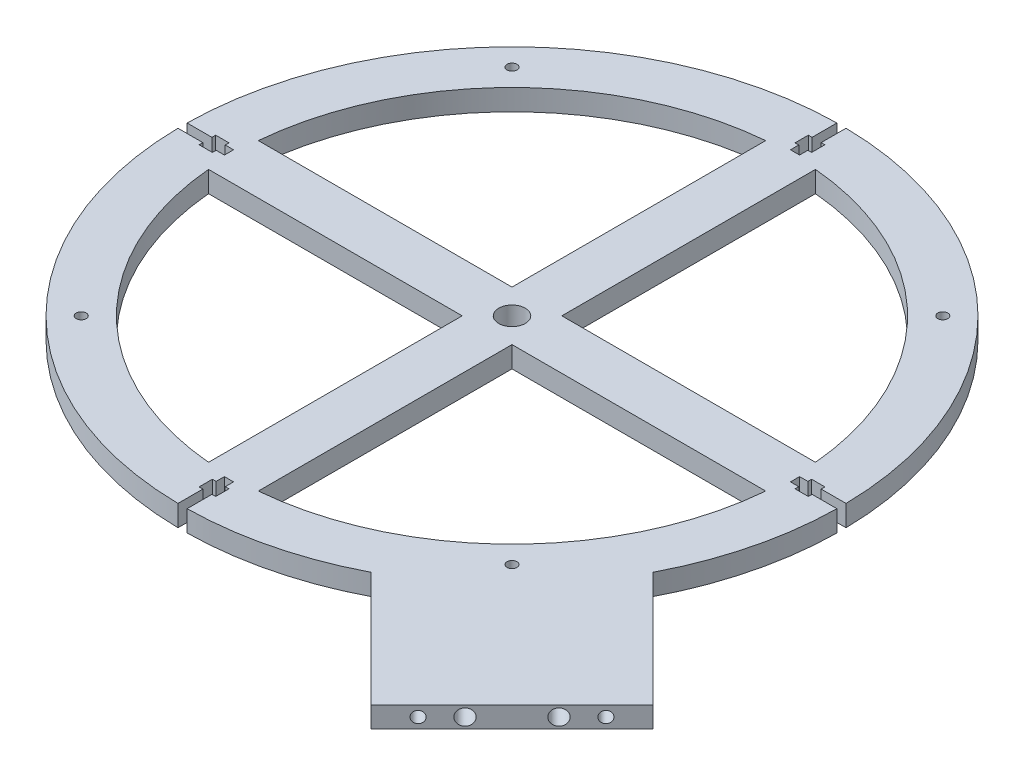
SolidWorks part; units mm, degrees
material "6061 Alloy"
ref_plane "Front Plane" through (0, 0, 0) normal (0, 0, 1) x (1, 0, 0)
ref_plane "Top Plane" through (0, 0, 0) normal (0, 1, 0) x (1, 0, 0)
ref_plane "Right Plane" through (0, 0, 0) normal (1, 0, 0) x (0, 0, -1)
sketch "Sketch1" plane through (0, 0, 0) normal (0, 1, 0) x (1, 0, 0)
  line L0 (0, -99.238) -> (0, 99.238) construction
  line L1 (-99.238, 0) -> (99.238, 0) construction
  line L2 (-98.9542, -7.5) -> (98.9542, -7.5)
  line L3 (7.5, -98.9542) -> (7.5, 98.9542)
  line L4 (-98.9542, 7.5) -> (98.9542, 7.5)
  line L5 (-7.5, -98.9542) -> (-7.5, 98.9542)
  line L6 (-7.5, -99.238) -> (-7.5, 99.238) construction
  line L7 (7.5, -99.238) -> (7.5, 99.238) construction
  line L8 (-99.238, -7.5) -> (99.238, -7.5) construction
  line L9 (-99.238, 7.5) -> (99.238, 7.5) construction
  line L11 (80.2566, -122.683) -> (122.683, -80.2566)
  line L16 (101.4698, -101.4698) -> (70.1719, -70.1719) construction
  line L17 (122.683, -80.2566) -> (88.1018, -45.6754)
  line L23 (80.2566, -122.683) -> (45.6754, -88.1018)
  line L33 (122.683, -80.2566) -> (91.3851, -48.9587) construction
  line L34 (80.2566, -122.683) -> (48.9587, -91.3851) construction
  circle A0 centre (0, 0) radius 100 construction
  circle A1 centre (0, 0) radius 99.238
  circle A2 centre (0, 0) radius 84.238
  point P7 (0, 0)
  point P11 (0, 0)
  dimension "D1" = 200
  dimension "D2" = 0.762
  dimension "D3" = 15
  dimension "D6" = 45
  dimension "D8" = 43.5
  dimension "D4" = 7.5
  dimension "D5" = 7.5
  dimension "D11" = 30
  dimension "D12" = 30
extrude "Boss-Extrude1" add sketch "Sketch1" along normal mid plane 6.35 contours A2 L2 A1 L5 | A2 L4 A1 L2 | A2 L5 A1 L4 | A2 L3 A1 L5 | A2 L4 A1 L3 | A2 L2 A1 L4 | A2 L3 A1 L2 | A2 L5 A1 L3 | L5 A2 L3 L2 | L4 A2 L2 L5 | L3 A2 L5 L4 | L2 A2 L4 L3 | L5 L2 L3 L4 | A1 | A1 L23 L17 region at (-91.6349, 0, 0) region at (-59.7933, 0, 59.7933) region at (-45.8134, 0, 0) region at (-59.7933, 0, -59.7933) region at (0, 0, 91.6349) region at (0, 0, 0) region at (0, 0, 45.8134) region at (0, 0, -91.6349) region at (59.7933, 0, 59.7933) region at (45.8134, 0, 0) region at (0, 0, -45.8134) region at (59.7933, 0, -59.7933) region at (85.2642, 0, 85.2642) region at (91.6349, 0, 0)
sketch "Sketch2" plane through (0, 0, 0) normal (0, 1, 0) x (1, 0, 0)
  line L0 (-1.375, 85.238) -> (-1.375, 99.238)
  line L1 (-1.375, 85.238) -> (1.375, 85.238)
  line L2 (-1.375, 99.238) -> (1.375, 99.238)
  line L3 (1.375, 85.238) -> (1.375, 99.238)
  line L4 (-1.375, 85.238) -> (1.375, 99.238) construction
  line L5 (-1.375, 99.238) -> (1.375, 85.238) construction
  line L6 (-2.5, 87.738) -> (-2.5, 91.738)
  line L7 (-2.5, 87.738) -> (2.5, 87.738)
  line L8 (-2.5, 91.738) -> (2.5, 91.738)
  line L9 (2.5, 87.738) -> (2.5, 91.738)
  line L10 (-2.5, 87.738) -> (2.5, 91.738) construction
  line L11 (-2.5, 91.738) -> (2.5, 87.738) construction
  line L12 (0, -1000) -> (0, 49000) construction
  line L13 (-1000, 0) -> (49000, 0) construction
  circle A0 centre (0, 0) radius 99.238 construction
  point P1 (0, 92.238)
  point P2 (0, 89.738)
  dimension "D1" = 2.75
  dimension "D2" = 14
  dimension "D3" = 4
  dimension "D4" = 5
  dimension "D5" = 2.5
extrude "Cut-Extrude1" cut sketch "Sketch2" against normal through all both and the other way through all contours L7 L0 L1 L3 | L8 L0 L7 L3 | L7 L9 L8 L3 | L0 L8 L3 L2 | L8 L6 L7 L0 region at (0, 0, -86.488) region at (-1.9375, 0, -89.738) region at (0, 0, -89.738) region at (0, 0, -95.488) region at (1.9375, 0, -89.738)
pattern_circular "CirPattern1" count 4 over 360 about axis through (0, 3.175, 0) along (0, 1, 0) of "Cut-Extrude1"
hole_wizard "Ø3.0 (3) Diameter Hole1" positions "Sketch3" profile "Sketch4" hole size "Ø3.0" standard "ANSI Metric" end condition up to next
sketch "Sketch3" plane through (0, 3.175, 0) normal (0, 1, 0) x (1, 0, 0)
  line L0 (-70.1719, -70.1719) -> (70.1719, 70.1719) construction
  line L2 (-70.1719, 70.1719) -> (70.1719, -70.1719) construction
  line L4 (70.1719, 70.1719) -> (59.5653, 59.5653)
  line L6 (70.1719, -70.1719) -> (59.5653, -59.5653)
  line L8 (-70.1719, -70.1719) -> (-59.5653, -59.5653)
  line L10 (-70.1719, 70.1719) -> (-59.5653, 59.5653)
  arc A2 (83.9035, 7.5) -> (7.5, 83.9035) centre (0, 0) ccw construction
  arc A3 (7.5, -83.9035) -> (83.9035, -7.5) centre (0, 0) ccw construction
  arc A4 (-83.9035, -7.5) -> (-7.5, -83.9035) centre (0, 0) ccw construction
  arc A5 (-7.5, 83.9035) -> (-83.9035, 7.5) centre (0, 0) ccw construction
  circle A6 centre (0, 0) radius 99.238
  arc A7 (-1.375, 99.2285) -> (-99.2285, 1.375) centre (0, 0) ccw construction
  point P107 (0, 0)
  point P324 (0, 0)
  point P360 (-64.8686, 64.8686)
  point P362 (64.8686, 64.8686)
  point P364 (64.8686, -64.8686)
  point P366 (-64.8686, -64.8686)
sketch "Sketch4" plane through (-64.8686, 3.175, 64.8686) normal (1, 0, 0) x (0, 0, 1)
  line L0 (0, 0) -> (0, 6.35)
  line L1 (0, 6.35) -> (1.5, 6.35)
  line L2 (1.5, 6.35) -> (1.5, 0)
  line L5 (1.5, 0) -> (0, 0)
  line L11 (0, -6.35) -> (0, 107.95) construction
  dimension "Thru Hole Dia." = 3
  dimension "Thru Hole Depth" = 6.35
hole_wizard "Ø8.0 (8) Diameter Hole1" positions "Sketch5" profile "Sketch6" hole size "Ø8.0" standard "ANSI Metric" end condition up to next
sketch "Sketch5" plane through (0, 3.175, 0) normal (0, 1, 0) x (1, 0, 0)
  point P0 (0, 0)
sketch "Sketch6" plane through (0, 3.175, 0) normal (1, 0, 0) x (0, 0, 1)
  line L0 (0, 0) -> (0, 6.35)
  line L1 (0, 6.35) -> (4, 6.35)
  line L2 (4, 6.35) -> (4, 0)
  line L5 (4, 0) -> (0, 0)
  line L11 (0, -6.35) -> (0, 107.95) construction
  dimension "Thru Hole Dia." = 8
  dimension "Thru Hole Depth" = 6.35
hole_wizard "#8-32 Tapped Hole1" positions "Sketch7" profile "Sketch8" tap size "#8-32" standard "ANSI Inch"
sketch "Sketch7" plane through (101.4698, 0, 101.4698) normal (0.7071, 0, 0.7071) x (0.7071, 0, -0.7071)
  line L0 (30, 3.175) -> (30, -3.175) construction
  line L1 (-30, 3.175) -> (-30, -3.175) construction
  point P0 (-20, 0)
  point P2 (20, 0)
  dimension "D1" = 10
  dimension "D2" = 10
sketch "Sketch8" plane through (87.3277, 0, 115.612) normal (0, 1, 0) x (0.7071, 0, -0.7071)
  line L0 (0, 0) -> (0, 11.7478)
  line L1 (0, 11.7478) -> (1.7272, 10.71)
  line L2 (1.7272, 10.71) -> (1.7272, 0)
  line L5 (1.7272, 0) -> (0, 0)
  line L10 (0, 11.7478) -> (-1.7272, 10.71) construction
  line L11 (0, -6.35) -> (0, 107.95) construction
  dimension "Tap Drill Dia." = 3.4544
  dimension "Tap Drill Depth" = 10.71
  dimension "Drill Angle" = 118
cosmetic thread "Hole Thread1" parameters "D1"=8.33, "D2"=4.1656
cosmetic thread "Hole Thread2" parameters "D1"=8.33, "D2"=4.1656
hole_wizard "3/16 (0.1875) Dowel Hole1" positions "Sketch9" profile "Sketch10" hole size "3/16" standard "ANSI Inch"
sketch "Sketch9" plane through (101.4698, 0, 101.4698) normal (0.7071, 0, 0.7071) x (0.7071, 0, -0.7071)
  line L0 (30, 3.175) -> (30, -3.175) construction
  line L1 (-30, 3.175) -> (-30, -3.175) construction
  point P0 (-10, 0)
  point P2 (10, 0)
  dimension "D1" = 20
  dimension "D2" = 20
sketch "Sketch10" plane through (94.3988, 0, 108.5409) normal (0, 1, 0) x (0.7071, 0, -0.7071)
  line L0 (0, 0) -> (0, 14.2608)
  line L1 (0, 14.2608) -> (2.3812, 12.83)
  line L2 (2.3812, 12.83) -> (2.3812, 0)
  line L5 (2.3812, 0) -> (0, 0)
  line L10 (0, 14.2608) -> (-2.3813, 12.83) construction
  line L11 (0, -6.35) -> (0, 107.95) construction
  dimension "Hole Dia." = 4.7625
  dimension "Hole Depth" = 12.83
  dimension "Drill Angle" = 118
